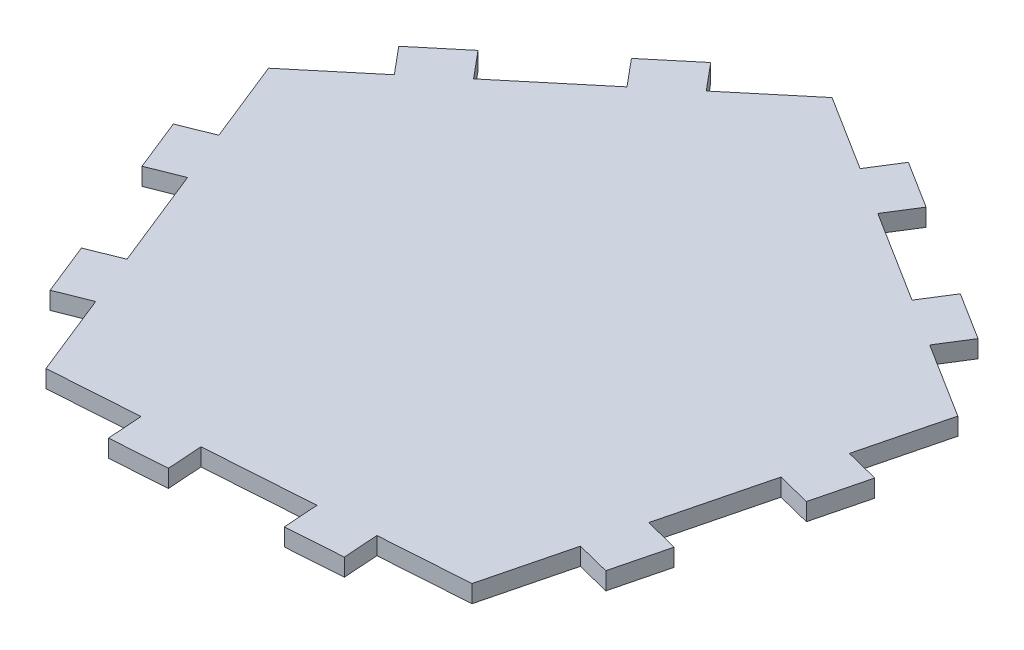
SolidWorks part; units mm, degrees
ref_plane "Front Plane" through (0, 0, 0) normal (0, 0, 1) x (1, 0, 0)
ref_plane "Top Plane" through (0, 0, 0) normal (0, 1, 0) x (1, 0, 0)
ref_plane "Right Plane" through (0, 0, 0) normal (1, 0, 0) x (0, 0, -1)
sketch "Sketch1" plane through (0, 0, 0) normal (0, 1, 0) x (1, 0, 0)
  line L1 (-59.9258, 15.1181) -> (-32.8962, -52.3211)
  line L2 (-32.8962, -52.3211) -> (39.5948, -47.4543)
  line L3 (39.5948, -47.4543) -> (57.3672, 22.9927)
  line L4 (57.3672, 22.9927) -> (-4.14, 61.6646)
  line L5 (-4.14, 61.6646) -> (-59.9258, 15.1181)
  circle A0 centre (0, 0) radius 50 construction
  dimension "D1" = 100
extrude "Boss-Extrude1" add sketch "Sketch1" along normal blind 3.18
ref_axis "Axis" through (0, 3.339, 0) along (0, -1, 0)
sketch "Axis Check" plane through (0, 3.18, 0) normal (0, 1, 0) x (1, 0, 0)
  line L0 (3.3493, -49.8877) -> (-4.14, 61.6646) construction
  line L1 (-32.8962, -52.3211) -> (39.5948, -47.4543) construction
  line L2 (57.3672, 22.9927) -> (-46.411, -18.6015) construction
  line L3 (-59.9258, 15.1181) -> (-32.8962, -52.3211) construction
  line L4 (-32.0329, 38.3913) -> (39.5948, -47.4543) construction
  line L5 (-4.14, 61.6646) -> (-59.9258, 15.1181) construction
  line L6 (-59.9258, 15.1181) -> (48.481, -12.2308) construction
  line L7 (39.5948, -47.4543) -> (57.3672, 22.9927) construction
  line L8 (-32.8962, -52.3211) -> (26.6136, 42.3287) construction
  line L9 (57.3672, 22.9927) -> (-4.14, 61.6646) construction
sketch "Sketch2" plane through (0, 0, 0) normal (0, -1, 0) x (1, 0, 0)
  line L0 (-53.8107, 0.1392) -> (-47.9072, -2.2269)
  line L1 (-53.8107, 0.1392) -> (-50.1723, 9.2172)
  line L2 (-47.9072, -2.2269) -> (-44.2688, 6.8511)
  line L3 (-50.1723, 9.2172) -> (-44.2688, 6.8511)
  line L4 (-59.9258, -15.1181) -> (-32.8962, 52.3211) construction
  line L5 (-42.6498, 27.9858) -> (-39.0113, 37.0638)
  line L6 (-42.6498, 27.9858) -> (-36.7463, 25.6197)
  line L7 (-39.0113, 37.0638) -> (-33.1079, 34.6977)
  line L8 (-36.7463, 25.6197) -> (-33.1079, 34.6977)
  line L9 (-46.411, 18.6015) -> (-19.2439, 7.7129) construction
  line L10 (-40.8306, 32.5248) -> (-34.9271, 30.1587) construction
  dimension "D1" = 6.36
  dimension "D2" = 9.78
  dimension "D3" = 10.11
extrude "Cut F" [suppressed] cut sketch "Sketch2" against normal through all
sketch "Sketch4" [suppressed] plane through (0, 3.18, 0) normal (0, 1, 0) x (1, 0, 0)
  line L9 (26.6136, 42.3287) -> (-26.6136, -42.3287) construction
  line L10 (57.3672, 22.9927) -> (-4.14, 61.6646) construction
  line L11 (-34.4964, -17.2915) -> (0.6335, 38.5824)
  line L12 (-34.4964, -17.2915) -> (-0.6335, -38.5824)
  line L13 (0.6335, 38.5824) -> (34.4964, 17.2915)
  line L14 (-0.6335, -38.5824) -> (34.4964, 17.2915)
  line L15 (-34.4964, -17.2915) -> (34.4964, 17.2915) construction
  line L16 (0.6335, 38.5824) -> (-0.6335, -38.5824) construction
  line L20 (0, 0) -> (39.0006, -24.5211) construction
  circle A0 centre (-21.8232, -34.7095) radius 3.25
  circle A1 centre (23.7041, -14.9036) radius 3.25
  point P5 (0, 0)
  point P6 (-21.8232, -34.7095)
  dimension "D3" = 6.5
  dimension "D1" = 40
  dimension "D2" = 66
  dimension "D4" = 8
  dimension "D5" = 8
extrude "Top Cut" [suppressed] cut sketch "Sketch4" against normal blind 10
sketch "Sketch7" [suppressed] plane through (0, 3.18, 0) normal (0, 1, 0) x (1, 0, 0)
  line L0 (0, 0) -> (26.6136, 42.3287) construction
  line L1 (57.3672, 22.9927) -> (-4.14, 61.6646) construction
  line L2 (-7.1857, -11.4287) -> (-30.8897, 3.4749) construction
  line L3 (-14.3588, -11.6437) -> (-33.0188, 0.0886) construction
  line L5 (0.6335, 38.5824) -> (-34.4964, -17.2915) construction
  circle A0 centre (-30.8897, 3.4749) radius 1
  circle A1 centre (-33.0188, 0.0886) radius 1
  dimension "D5" = 2
  dimension "D1" = 4
  dimension "D2" = 17.5
  dimension "D3" = 8
  dimension "D4" = 8
extrude "Top Cut 2" [suppressed] cut sketch "Sketch7" against normal through all
sketch "Sketch10" [suppressed] plane through (0, 3.18, 0) normal (0, 1, 0) x (1, 0, 0)
  line L0 (26.6136, 42.3287) -> (17.565, 27.9369) construction
  line L1 (57.3672, 22.9927) -> (-4.14, 61.6646) construction
  line L2 (34.4964, 17.2915) -> (0.6335, 38.5824) construction
  line L3 (30.1304, 27.124) -> (10.6872, 39.3486) construction
  circle A0 centre (14.8326, 36.7423) radius 1
  circle A1 centre (26.6846, 29.2905) radius 1
  dimension "D1" = 6
  dimension "D2" = 2
  dimension "D3" = 7
extrude "Top Cut 3" [suppressed] cut sketch "Sketch10" against normal blind 10
sketch "Sketch8" [suppressed] plane through (0, 3.18, 0) normal (0, 1, 0) x (1, 0, 0)
  line L0 (3.3493, -49.8877) -> (-4.14, 61.6646) construction
  line L5 (-32.8962, -52.3211) -> (39.5948, -47.4543) construction
  line L6 (-17.9455, -31.2723) -> (21.9647, -28.5929)
  line L11 (-17.9455, -31.2723) -> (-21.9647, 28.5929)
  line L12 (21.9647, -28.5929) -> (17.9455, 31.2723)
  line L13 (-21.9647, 28.5929) -> (17.9455, 31.2723)
  point P4 (1.4955, -22.2759)
  dimension "D1" = 60
  dimension "D2" = 40
  dimension "D3" = 20
extrude "Bottom Cut" [suppressed] cut sketch "Sketch8" against normal blind 10
sketch "Sketch9" [suppressed] plane through (0, 3.18, 0) normal (0, 1, 0) x (1, 0, 0)
  line L0 (19.9551, 1.3397) -> (-19.9551, -1.3397) construction
  line L1 (21.9647, -28.5929) -> (17.9455, 31.2723) construction
  line L2 (-21.9647, 28.5929) -> (-17.9455, -31.2723) construction
  line L3 (-19.9551, -1.3397) -> (-44.4689, -2.9855) construction
  line L4 (19.9551, 1.3397) -> (42.6839, 2.8657) construction
  line L5 (-32.8962, -52.3211) -> (39.5948, -47.4543) construction
  line L6 (-29.6051, -6.8886) -> (-32.3788, -7.0748)
  line L7 (-29.6051, -6.8886) -> (-30.2602, 2.8694)
  line L8 (-30.2602, 2.8694) -> (-33.0339, 2.6832)
  line L9 (-32.3788, -7.0748) -> (-33.0339, 2.6832)
  line L10 (-29.6051, -6.8886) -> (-33.0339, 2.6832) construction
  line L11 (-30.2602, 2.8694) -> (-32.3788, -7.0748) construction
  line L12 (33.0339, -2.6832) -> (30.2602, -2.8694)
  line L13 (33.0339, -2.6832) -> (32.3788, 7.0748)
  line L14 (32.3788, 7.0748) -> (29.6051, 6.8886)
  line L15 (30.2602, -2.8694) -> (29.6051, 6.8886)
  line L16 (33.0339, -2.6832) -> (29.6051, 6.8886) construction
  line L17 (32.3788, 7.0748) -> (30.2602, -2.8694) construction
  line L18 (-32.8962, -52.3211) -> (39.5948, -47.4543) construction
  point P6 (-31.3195, -2.1027)
  point P13 (31.3195, 2.1027)
  dimension "D1" = 9.78
  dimension "D4" = 9.78
  dimension "D5" = 10
  dimension "D6" = 10
  dimension "D2" = 2.78
  dimension "D3" = 2.78
extrude "Battery Holder Cut" [suppressed] cut sketch "Sketch9" against normal blind 6.36
sketch "Sketch3" plane through (0, 3.18, 0) normal (0, 1, 0) x (1, 0, 0)
  line L0 (0, 0) -> (-40.9819, 49.1167) construction
  line L1 (-51.5485, 30.3911) -> (-43.3993, 20.6243)
  line L3 (-43.3993, 20.6243) -> (-35.5521, 27.1718)
  line L4 (-43.7013, 36.9386) -> (-35.5521, 27.1718)
  line L5 (-4.14, 61.6646) -> (-59.9258, 15.1181) construction
  line L6 (-71.9961, 5.0469) -> (-69.9588, 2.6052)
  line L7 (-71.9961, 5.0469) -> (-47.4739, 25.5077)
  line L14 (-28.5137, 49.6108) -> (-20.3645, 39.8441)
  line L16 (-20.3645, 39.8441) -> (-12.5173, 46.3916)
  line L17 (-20.6665, 56.1583) -> (-12.5173, 46.3916)
  line L18 (-40.5017, 25.1278) -> (-39.4757, 23.8981) construction
  line L19 (-51.5485, 30.3911) -> (-43.7013, 36.9386)
  line L21 (-28.5137, 49.6108) -> (-20.6665, 56.1583)
  line L22 (-16.5919, 51.275) -> (4.7866, 69.1127)
  line L23 (-39.6267, 32.0552) -> (-24.4391, 44.7274)
  line M18 (-4.14, 61.6646) -> (-59.9258, 15.1181)
  dimension "D1" = 12.72
  dimension "D2" = 10.22
  dimension "D3" = 9.89
  dimension "D4" = 100
extrude "Extrude M" add sketch "Sketch3" against normal up to surface (3.18 mm away) contours L21 L14 L7 L17 | L19 L1 L4 M18 region at (-45.5876, 3.18, -31.2231) region at (-22.5528, 3.18, -50.4429) up to face at (0, 0, 0)
pattern_circular "Circle F" [suppressed] count 5 over 360 about axis through (0, 3.339, 0) along (0, -1, 0) of bodies 102
pattern_circular "Circle M" count 5 over 360 about axis through (0, 3.339, 0) along (0, -1, 0) of "Extrude M"
pattern_circular "Circle Side F" [suppressed] count 5 over 360 about axis through (0, 3.339, 0) along (0, -1, 0) of bodies 173
pattern_circular "Circle Side M" [suppressed] count 5 over 360 about axis through (0, 3.339, 0) along (0, -1, 0) of bodies 168
equation "\"kerf\"= .22mm"
equation "\"tabWidthF\"= 10 - \"kerf\""
equation "\"tabThickness\" = 6.36mm"
equation "\"D1@Sketch2\"=\"tabThickness\""
equation "\"tabWidthM\"= 10 + \"kerf\""
equation "\"halfkerf\"= \"kerf\" / 2.00mm"
equation "\"D1@Sketch9\"=\"tabWidthF\""
equation "\"D4@Sketch9\"=\"tabWidthF\""
equation "\"D1@Battery Holder Cut\" = \"tabThickness\""
equation "\"tabLength\" = \"kerf\" + 12"
